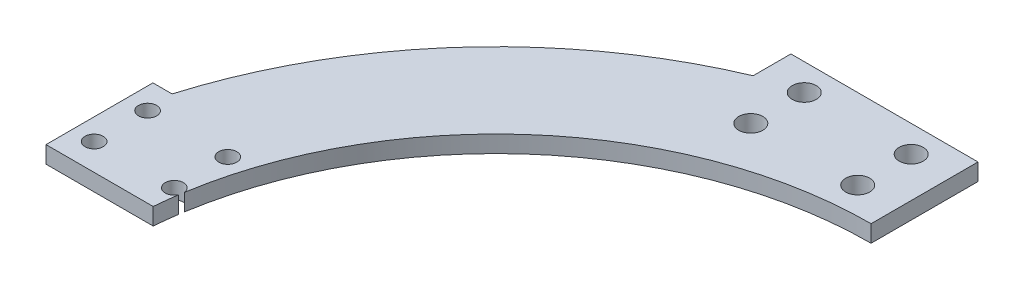
SolidWorks part; units mm, degrees
material "6061-T6 (SS)"
ref_plane "Front Plane" through (0, 0, 0) normal (0, 0, 1) x (1, 0, 0)
ref_plane "Top Plane" through (0, 0, 0) normal (0, 1, 0) x (1, 0, 0)
ref_plane "Right Plane" through (0, 0, 0) normal (1, 0, 0) x (0, 0, -1)
sketch "Sketch1" plane through (0, 0, 0) normal (0, 1, 0) x (1, 0, 0)
  line L2 (-89.9792, 0.6445) -> (-69.9256, 0.6445)
  line L3 (0, 85) -> (0, 65)
  arc A0 (0, 85) -> (-89.9792, 0.6445) centre (0, -5.1667) ccw
  arc A3 (0, 75) -> (-80, 0) centre (0, -5.1667) ccw
  arc A4 (0, 65) -> (-70.0208, -0.6445) centre (0, -5.1667) ccw
  dimension "D1" = 10
  dimension "D3" = 80
  dimension "D4" = 75
  dimension "D2" = 10
extrude "Boss-Extrude1" add sketch "Sketch1" along normal blind 3.175 contours A4 L3 A3 L2 | A3 L3 A0 L2 region at (-60.8251, 0, -59.7135) region at (-53.8496, 0, -52.7388)
sketch "Sketch2" plane through (0, 3.175, 0) normal (0, 1, 0) x (1, 0, 0)
  line L0 (-89.9792, 0.6445) -> (-89.9792, 20.6445)
  line L1 (-89.9792, 20.6445) -> (-69.9256, 20.6445)
  line L2 (-69.9256, 20.6445) -> (-69.9256, 0.6445)
  line L4 (0, 65) -> (-35, 65)
  line L7 (-89.9792, 0.6445) -> (-69.9256, 0.6445)
  line L8 (0, 65) -> (0, 85)
  line L9 (0, 65) -> (0, 85)
  line L10 (0, 85) -> (-35, 85)
  line L11 (-35, 65) -> (-35, 85)
  dimension "D1" = 20
  dimension "D3" = 35
  dimension "D2" = 20
extrude "Boss-Extrude2" add sketch "Sketch2" against normal up to surface (3.175 mm away) contours L1 L0 | L11 L10 region at (-79.9524, 3.175, -10.6445) region at (-17.5, 3.175, -75) up to face at (-47.2844, 0, -45.68)
hole_wizard "M4 Clearance Hole1" positions "Sketch6" profile "Sketch4" hole size "M4" standard "ANSI Metric" end condition through all
sketch "Sketch6" plane through (0, 0, 0) normal (0, 1, 0) x (1, 0, 0)
  line L1 (-27.5, 70) -> (-7.5, 70)
  line L2 (-27.5, 70) -> (-27.5, 80)
  line L3 (-27.5, 80) -> (-7.5, 80)
  line L4 (-7.5, 70) -> (-7.5, 80)
  line L14 (0, 85) -> (-35, 85) construction
  line L17 (0, 85) -> (0, 65) construction
  point P3 (-27.5, 70)
  point P4 (-7.5, 80)
  point P83 (-27.5, 80)
  point P84 (-7.5, 70)
  point P172 (-17.5, 85)
  point P190 (-17.5, 80)
  point P192 (-7.5, 75)
  point P195 (0, 75)
  dimension "D1" = 10
  dimension "D2" = 20
sketch "Sketch4" plane through (-27.5, 0, -70) normal (1, 0, 0) x (0, 0, -1)
  line L0 (0, 0) -> (0, 3.175)
  line L1 (0, 3.175) -> (2.25, 3.175)
  line L2 (2.25, 3.175) -> (2.25, 0)
  line L5 (2.25, 0) -> (0, 0)
  line L11 (0, -6.35) -> (0, 107.95) construction
  dimension "Thru Hole Dia." = 4.5
  dimension "Thru Hole Depth" = 3.175
sketch "Sketch7" plane through (0, 0, 0) normal (0, -1, 0) x (1, 0, 0)
  line L1 (-85.9792, -15.6445) -> (-70.9792, -15.6445) construction
  line L2 (-85.9792, -15.6445) -> (-85.9792, -5.6445) construction
  line L3 (-85.9792, -5.6445) -> (-70.9792, -5.6445) construction
  line L4 (-70.9792, -15.6445) -> (-70.9792, -5.6445) construction
  line L5 (-89.9792, -0.6445) -> (-69.9256, -0.6445) construction
  line L6 (-89.9792, -20.6445) -> (-89.9792, -0.6445) construction
  circle A0 centre (-70.9792, -15.6445) radius 1.7
  circle A1 centre (-85.9792, -15.6445) radius 1.7
  circle A2 centre (-85.9792, -5.6445) radius 1.7
  circle A3 centre (-70.9792, -5.6445) radius 1.7
  dimension "D3" = 3.4
  dimension "D1" = 10
  dimension "D2" = 15
  dimension "D4" = 5
  dimension "D5" = 4
extrude "Cut-Extrude1" cut sketch "Sketch7" against normal through all
